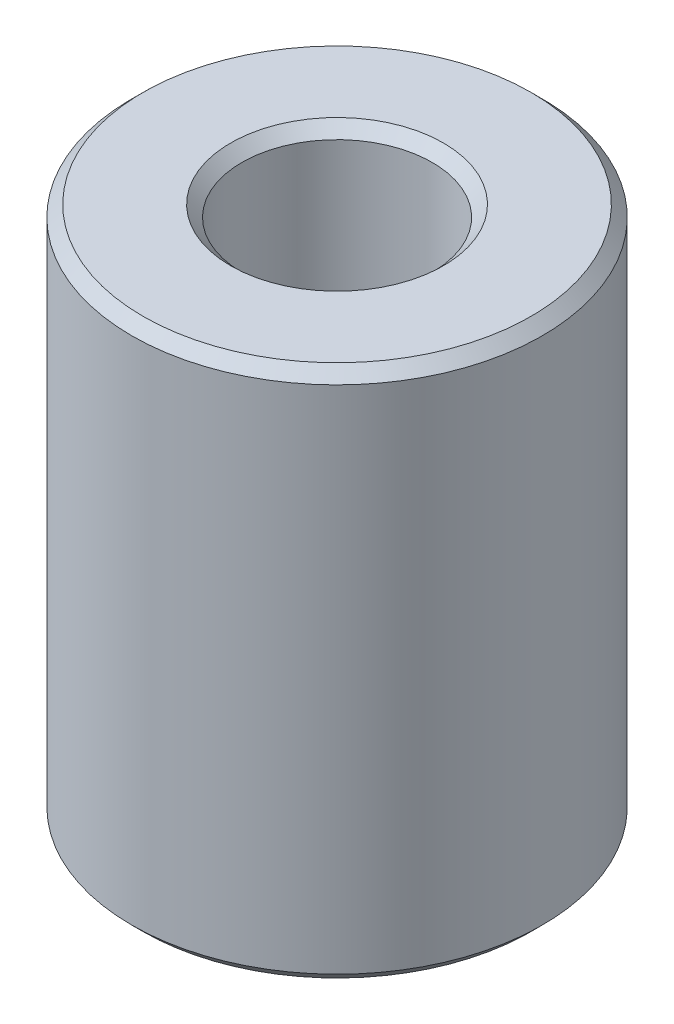
SolidWorks part; units mm, degrees
ref_plane "Front Plane" through (0, 0, 0) normal (0, 0, 1) x (1, 0, 0)
ref_plane "Top Plane" through (0, 0, 0) normal (0, 1, 0) x (1, 0, 0)
ref_plane "Right Plane" through (0, 0, 0) normal (1, 0, 0) x (0, 0, -1)
sketch "Sketch1" plane through (0, 0, 0) normal (0, 1, 0) x (1, 0, 0)
  circle A0 centre (0, 0) radius 7.5
  dimension "SLEEVE_OD" = 15
extrude "Boss-Extrude1" add sketch "Sketch1" along normal blind 19.4729
sketch "Sketch2" plane through (0, 0, 0) normal (0, 1, 0) x (1, 0, 0)
  circle A0 centre (0, 0) radius 3.4779
  dimension "BORE_D" = 6.9559
extrude "Cut-Extrude1" cut sketch "Sketch2" along normal through all
chamfer "Chamfer1" distance 0.4105 angle 45 4 edges at (0, 19.4729, 3.4779) (0, 0, 3.4779) (0, 0, 7.5) (0, 19.4729, 7.5)
